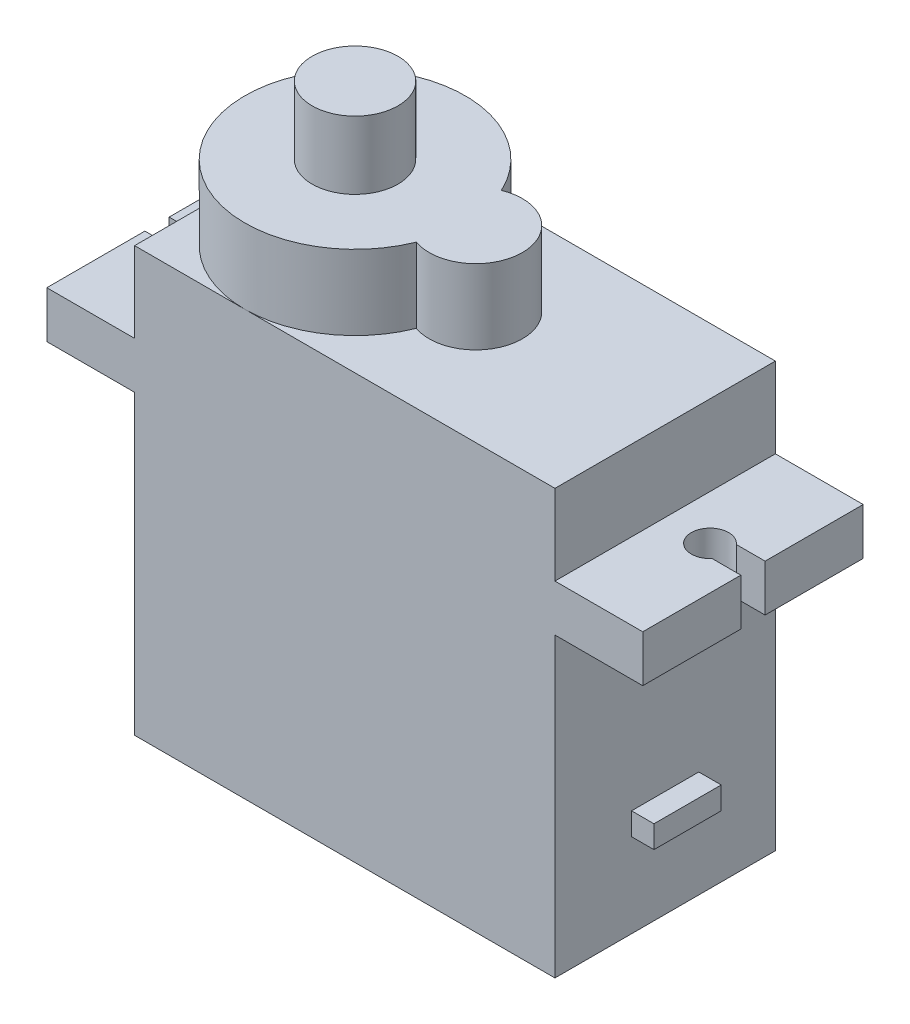
SolidWorks part; units mm, degrees
ref_plane "Plan de face" through (0, 0, 0) normal (0, 0, 1) x (1, 0, 0)
ref_plane "Plan de dessus" through (0, 0, 0) normal (0, 1, 0) x (1, 0, 0)
ref_plane "Plan de droite" through (0, 0, 0) normal (1, 0, 0) x (0, 0, -1)
sketch "Esquisse1" plane through (0, 0, 0) normal (0, 0, 1) x (1, 0, 0)
  line L0 (0, 0) -> (-22.5, 0)
  line L1 (-22.5, 0) -> (-22.5, 15.9)
  line L2 (-22.5, 15.9) -> (-27.2, 15.9)
  line L3 (-27.2, 15.9) -> (-27.2, 18.4)
  line L4 (-27.2, 18.4) -> (-22.5, 18.4)
  line L5 (-22.5, 18.4) -> (-22.5, 22.7)
  line L6 (-22.5, 22.7) -> (0, 22.7)
  line L7 (0, 22.7) -> (0, 18.4)
  line L8 (0, 18.4) -> (4.7, 18.4)
  line L9 (4.7, 18.4) -> (4.7, 15.9)
  line L10 (4.7, 15.9) -> (0, 15.9)
  line L11 (0, 15.9) -> (0, 0)
  line L12 (-22.5, 15.9) -> (0, 15.9) construction
  line L13 (0, 18.4) -> (-22.5, 18.4) construction
  line L14 (-22.5, 18.4) -> (-22.5, 15.9) construction
  line L15 (0, 15.9) -> (0, 18.4) construction
  dimension "D1" = 22.5
  dimension "D2" = 15.9
  dimension "D3" = 2.5
  dimension "D4" = 4.3
  dimension "D5" = 4.7
  dimension "D6" = 4.7
extrude "Boss.-Extru.1" add sketch "Esquisse1" along normal blind 11.8 contours L1 L2 L3 L4 L5 L6 L7 L8 L9 L10 L11 L0
sketch "Esquisse2" plane through (0, 22.7, 0) normal (0, 1, 0) x (1, 0, 0)
  line L0 (-22.5, -11.8) -> (-22.5, 0) construction
  line L1 (-22.5, -11.8) -> (0, -11.8) construction
  circle A1 centre (-16.6, -5.9) radius 5.9
  dimension "D1" = 11.8
  dimension "D2" = 5.9
  dimension "D3" = 5.9
sketch "Esquisse3" plane through (0, 22.7, 0) normal (0, 1, 0) x (1, 0, 0)
  line L0 (0, -11.8) -> (0, 0) construction
  circle A0 centre (-10.3, -5.7384) radius 2.5
  dimension "D1" = 5
  dimension "D2" = 10.3
extrude "Boss.-Extru.3" add sketch "Esquisse2" along normal blind 4 contours A1
extrude "Boss.-Extru.4" add sketch "Esquisse3" along normal blind 4 contours A0
sketch "Esquisse5" plane through (0, 26.7, 0) normal (0, 1, 0) x (1, 0, 0)
  circle A0 centre (-16.6, -5.9) radius 2.3
  arc A2 (-11.2448, -3.4238) -> (-11.1249, -8.0984) centre (-16.6, -5.9) ccw construction
  dimension "D1" = 4.6
  dimension "D2" = 0
extrude "Boss.-Extru.5" add sketch "Esquisse5" along normal blind 3.63 contours A0
sketch "Esquisse6" plane through (0, 18.4, 0) normal (0, 1, 0) x (1, 0, 0)
  line L0 (0, 0) -> (4.7, 0) construction
  line L1 (4.7, -11.8) -> (4.7, 0) construction
  line L2 (6.6619, -5.9) -> (6.6619, -5.25)
  line L3 (6.6619, -5.9) -> (6.6619, -6.55)
  line L11 (6.6619, -6.55) -> (3.1599, -6.55)
  line L12 (6.6619, -5.25) -> (3.1599, -5.25)
  line L13 (2.4, -5.9) -> (6.6619, -5.9) construction
  line L14 (0, -11.8) -> (-22.5, -11.8) construction
  line L15 (-11.25, -11.8) -> (-11.25, 0) construction
  line L16 (0, 0) -> (-22.5, 0) construction
  line L17 (-24.9, -5.9) -> (-29.1619, -5.9) construction
  line L18 (-29.1619, -5.25) -> (-25.6599, -5.25)
  line L19 (-29.1619, -6.55) -> (-25.6599, -6.55)
  line L20 (-29.1619, -5.9) -> (-29.1619, -6.55)
  line L21 (-29.1619, -5.9) -> (-29.1619, -5.25)
  circle A0 centre (2.4, -5.9) radius 1 construction
  arc A1 (3.1599, -6.55) -> (3.1599, -5.25) centre (2.4, -5.9) cw
  circle A2 centre (-24.9, -5.9) radius 1 construction
  arc A3 (-25.6599, -6.55) -> (-25.6599, -5.25) centre (-24.9, -5.9) ccw
  dimension "D1" = 2
  dimension "D2" = 5.9
  dimension "D3" = 2.3
  dimension "D4" = 0.65
  dimension "D5" = 0.65
  dimension "D6" = 3.502
extrude "Enlèv. mat.-Extru.7" cut sketch "Esquisse6" against normal up to next
sketch "Esquisse7" plane through (0, 0, 0) normal (1, 0, 0) x (0, 0, -1)
  line L1 (-7.7, 5.7) -> (-4.1, 5.7)
  line L2 (-7.7, 5.7) -> (-7.7, 4.5)
  line L3 (-7.7, 4.5) -> (-4.1, 4.5)
  line L4 (-4.1, 5.7) -> (-4.1, 4.5)
  line L5 (-11.8, 0) -> (0, 0) construction
  line L6 (-5.9, 0) -> (-5.9, 4.5) construction
  dimension "D1" = 3.6
  dimension "D2" = 1.2
  dimension "D3" = 4.5
extrude "Boss.-Extru.7" add sketch "Esquisse7" along normal blind 1.2
sketch "Esquisse11" plane through (0, 30.33, 0) normal (0, 1, 0) x (1, 0, 0)
  line L0 (-16.6, -5.9) -> (-18.9, -5.9) construction
  circle A0 centre (-16.6, -5.9) radius 2.3 construction
sketch "Esquisse14" plane through (0, 26.7, 0) normal (0, 1, 0) x (1, 0, 0)
  line L0 (-16.6, -5.9) -> (-18.9, -5.9) construction
  line L1 (-16.6, -5.9) -> (-16.6, -8.2) construction
  circle A0 centre (-16.6, -5.9) radius 2.3 construction
move or copy body "Corps-Déplacer/Copier1" [suppressed] bodies to move or copy 108
